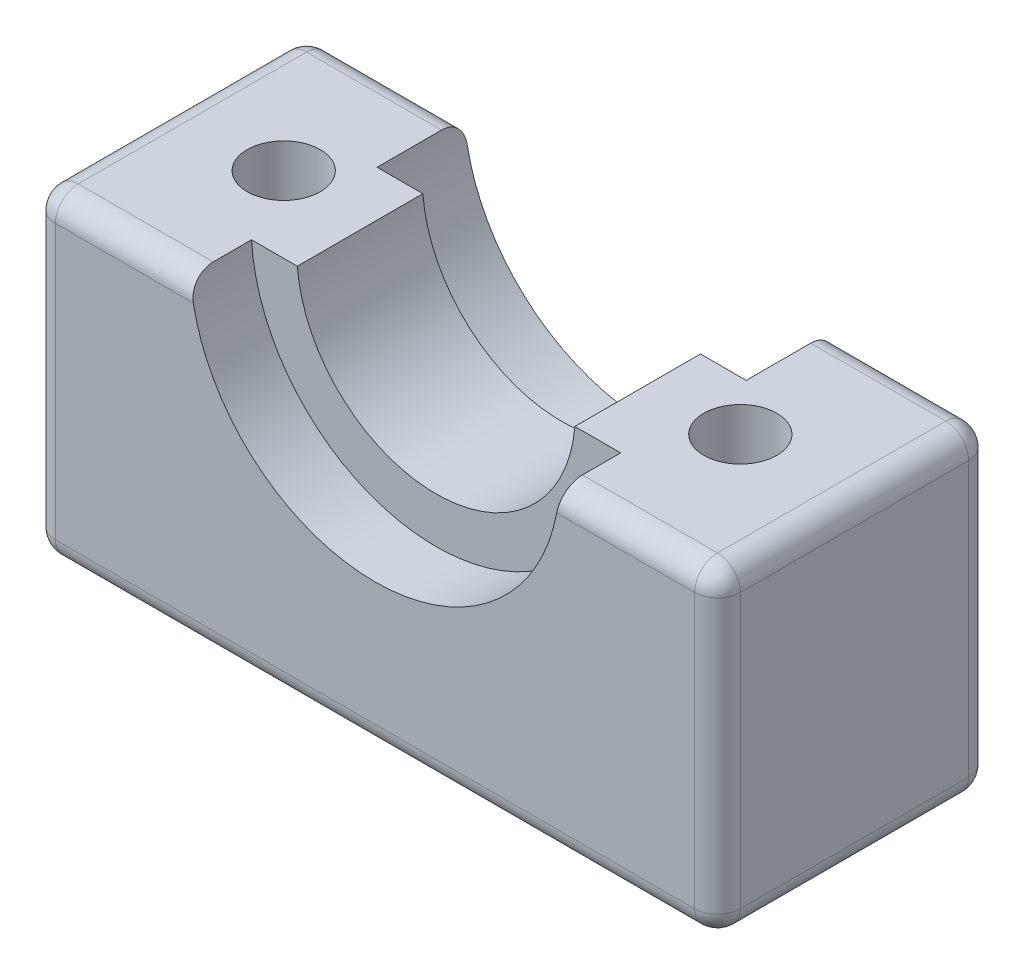
SolidWorks part; units mm, degrees
ref_plane "Спереди" through (0, 0, 0) normal (0, 0, 1) x (1, 0, 0)
ref_plane "Сверху" through (0, 0, 0) normal (0, 1, 0) x (1, 0, 0)
ref_plane "Справа" through (0, 0, 0) normal (1, 0, 0) x (0, 0, -1)
sketch "Эскиз1" plane through (0, 0, 0) normal (0, 0, 1) x (1, 0, 0)
  line L1 (-15, -7) -> (15, -7)
  line L2 (-15, -7) -> (-15, 7)
  line L3 (-15, 7) -> (15, 7)
  line L4 (15, -7) -> (15, 7)
  line L5 (-15, -7) -> (15, 7) construction
  line L6 (-15, 7) -> (15, -7) construction
  point P0 (0, 0)
  dimension "D1" = 14
  dimension "D2" = 30
extrude "Бобышка-Вытянуть1" add sketch "Эскиз1" along normal blind 12
ref_plane "Плоскость1" through (0, 7.5, 0) normal (0, 1, 0) x (1, 0, 0)
sketch "Эскиз2" plane through (0, 7.5, 0) normal (0, 1, 0) x (1, 0, 0)
  line L0 (0, 4.4138) -> (0, -16.522) construction
  line L1 (0, 0) -> (0, -12)
  line L2 (15, -12) -> (-15, -12) construction
  line L3 (0, -12) -> (8.1, -12)
  line L4 (8.1, -12) -> (8.1, -9.325)
  line L5 (8.1, -9.325) -> (6.1, -9.325)
  line L6 (6.1, -9.325) -> (6.1, -3.825)
  line L7 (6.1, -3.825) -> (8.1, -3.825)
  line L8 (8.1, -3.825) -> (8.1, 0)
  line L9 (15, 0) -> (-15, 0) construction
  line L10 (0, 0) -> (8.1, 0)
  dimension "D1" = 5.5
  dimension "D2" = 2.675
  dimension "D3" = 12.2
  dimension "D4" = 16.2
revolve "Вырез-Повернуть1" cut sketch "Эскиз2" angle 360 about L0
fillet "Скругление1" radius 1 14 edges at (-15, -7, 6) (0, -7, 0) (15, -7, 6) (0, -7, 12) (11.5423, 7, 12) (-11.5423, 7, 12) (-11.5423, 7, 0) (11.5423, 7, 0) (15, 0, 12) (15, 0, 0) (-15, 0, 12) (-15, 0, 0) (-15, 7, 6) (15, 7, 6)
sketch "Эскиз3" plane through (0, -7, 0) normal (0, -1, 0) x (1, 0, 0)
  line L0 (-10, 6) -> (10, 6) construction
  line L1 (-14, 11) -> (-14, 1) construction
  line L2 (0, 16.5483) -> (0, -5.8765) construction
  circle A0 centre (-10, 6) radius 3.25
  circle A1 centre (10, 6) radius 3.25
  circle A2 centre (-10, 6) radius 1.6
  circle A3 centre (10, 6) radius 1.6
  point P2 (-14, 6)
  point P12 (0, 6)
  dimension "D1" = 6.5
  dimension "D2" = 3.2
  dimension "D3" = 20
extrude "Вырез-Вытянуть1" cut sketch "Эскиз3" against normal through all contours A2 | A3
extrude "Вырез-Вытянуть2" cut sketch "Эскиз3<3>" against normal blind 3 contours A0 | A1
sketch "Эскиз3<3>" plane through (0, -7, 0) normal (0, -1, 0) x (1, 0, 0) same geometry as "Эскиз3"
fillet "Скругление2" radius 1 2 edges at (10, -7, 2.75) (-10, -7, 2.75)
